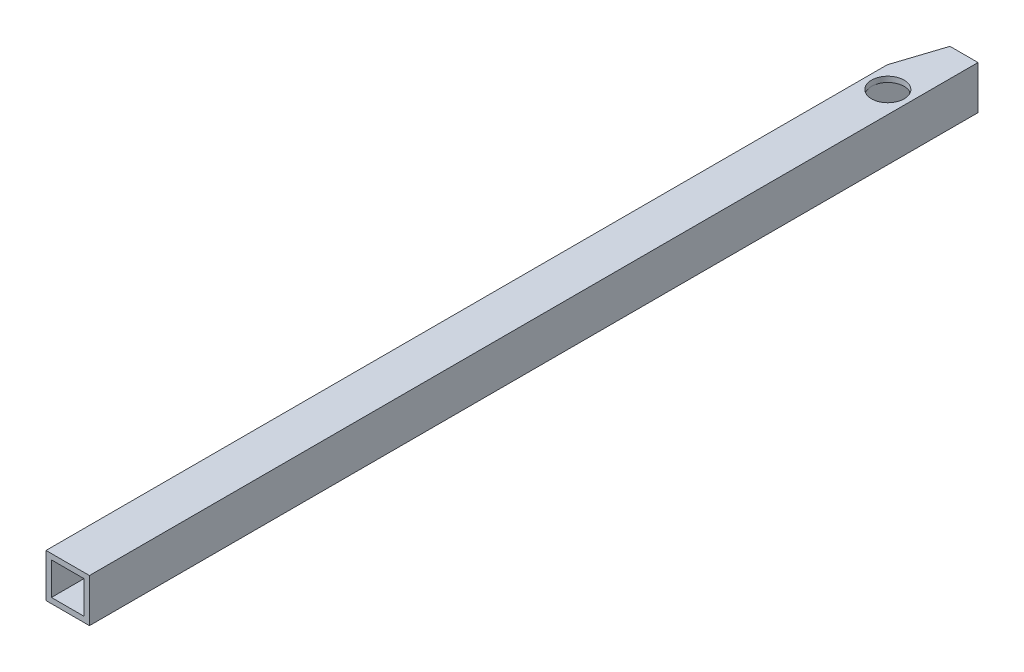
SolidWorks part; units mm, degrees
ref_plane "Front Plane" through (0, 0, 0) normal (0, 0, 1) x (1, 0, 0)
ref_plane "Top Plane" through (0, 0, 0) normal (0, 1, 0) x (1, 0, 0)
ref_plane "Right Plane" through (0, 0, 0) normal (1, 0, 0) x (0, 0, -1)
sketch "Sketch1" plane through (0, 0, 0) normal (0, 0, 1) x (1, 0, 0)
  line L0 (-9.525, 9.525) -> (9.525, 9.525)
  line L2 (-12.7, 12.7) -> (12.7, 12.7)
  line L3 (-12.7, 12.7) -> (-12.7, -12.7)
  line L4 (-12.7, -12.7) -> (12.7, -12.7)
  line L5 (12.7, 12.7) -> (12.7, -12.7)
  line L10 (9.525, 9.525) -> (9.525, -9.525)
  line L11 (-9.525, -9.525) -> (9.525, -9.525)
  line L12 (-9.525, 9.525) -> (-9.525, -9.525)
  point P12 (0, 12.7)
  point P14 (12.7, 0)
  dimension "Wall Thickness" = 3.175
  dimension "Outside Width" = 25.4
  dimension "Outside Height" = 25.4
  dimension "Inside Height" = 19.05
  dimension "Inside Width" = 19.05
sketch "Sketch2" plane through (0, 0, 0) normal (1, 0, 0) x (0, 0, -1)
  line L0 (266.7, 0) -> (-266.7, 0)
  point P4 (0, 0)
  point P7 (-266.7, 0)
  point P10 (266.7, 0)
  dimension "Length" = 533.4
sketch "Sketch3" plane through (0, 0, 0) normal (0, 0, 1) x (1, 0, 0)
  line L21 (12.7, 12.7) -> (-12.7, 12.7)
  line L22 (12.7, -12.7) -> (12.7, 12.7)
  line L23 (-12.7, -12.7) -> (12.7, -12.7)
  line L24 (-12.7, 12.7) -> (-12.7, -12.7)
  line L25 (12.7, 12.7) -> (-12.7, 12.7)
  line L26 (12.7, -12.7) -> (12.7, 12.7)
  line L27 (-12.7, -12.7) -> (12.7, -12.7)
  line L28 (-12.7, 12.7) -> (-12.7, -12.7)
  line L29 (9.525, 9.525) -> (-9.525, 9.525)
  line L30 (9.525, -9.525) -> (9.525, 9.525)
  line L31 (-9.525, -9.525) -> (9.525, -9.525)
  line L32 (-9.525, 9.525) -> (-9.525, -9.525)
  line L33 (9.525, 9.525) -> (-9.525, 9.525)
  line L34 (9.525, -9.525) -> (9.525, 9.525)
  line L35 (-9.525, -9.525) -> (9.525, -9.525)
  line L36 (-9.525, 9.525) -> (-9.525, -9.525)
  dimension "D1" = 0
  dimension "D2" = 0
extrude "Boss-Extrude1" add sketch "Sketch3" along normal up to vertex (266.7 mm away) and the other way up to vertex (266.7 mm away) up to point (0, 0, 266.7) other way up to point (0, 0, -266.7)
sketch "Drawing Reference" plane through (0, 0, 0) normal (1, 0, 0) x (0, 0, -1)
  line L0 (-266.7, 0) -> (266.7, 0) construction
  line L1 (0, -12.7) -> (0, 12.7) construction
  line L2 (-266.7, -12.7) -> (266.7, -12.7) construction
  line L5 (-266.7, 12.7) -> (266.7, 12.7) construction
  point P7 (-248.412, 0)
  point P8 (248.412, 0)
  dimension "D1" = 18.288
sketch "Sketch4" plane through (0, 12.7, 0) normal (0, 1, 0) x (1, 0, 0)
  line L1 (0, 266.7) -> (0, 212.725) construction
  line L7 (-12.7, 225.0135) -> (-12.7, 266.7)
  line L8 (-188.9197, -317.3351) -> (4.6184, 278.3139) construction
  line L10 (-12.7, -266.7) -> (-12.7, 266.7) construction
  line L11 (-12.7, 266.7) -> (12.7, 266.7)
  line L12 (12.7, 266.7) -> (12.7, 252.73)
  line L13 (12.7, -266.7) -> (12.7, 266.7) construction
  line L14 (12.7, 252.73) -> (-3.6943, 252.73)
  line L15 (-3.6943, 252.73) -> (-12.7, 225.0135)
  circle A0 centre (0, 212.725) radius 9.525
  dimension "D1" = 13.97
extrude "Cut-Extrude1" cut sketch "Sketch4" against normal blind 25.4
sketch "Sketch5" plane through (0, -12.7, 0) normal (0, -1, 0) x (1, 0, 0)
  circle A0 centre (-0.6605, -179.8709) radius 9.525
extrude "Cut-Extrude2" cut sketch "Sketch5" against normal blind 3.175
equation "\"D1@Drawing Reference\"=\"Outside Width@Sketch1\" * 0.72"
